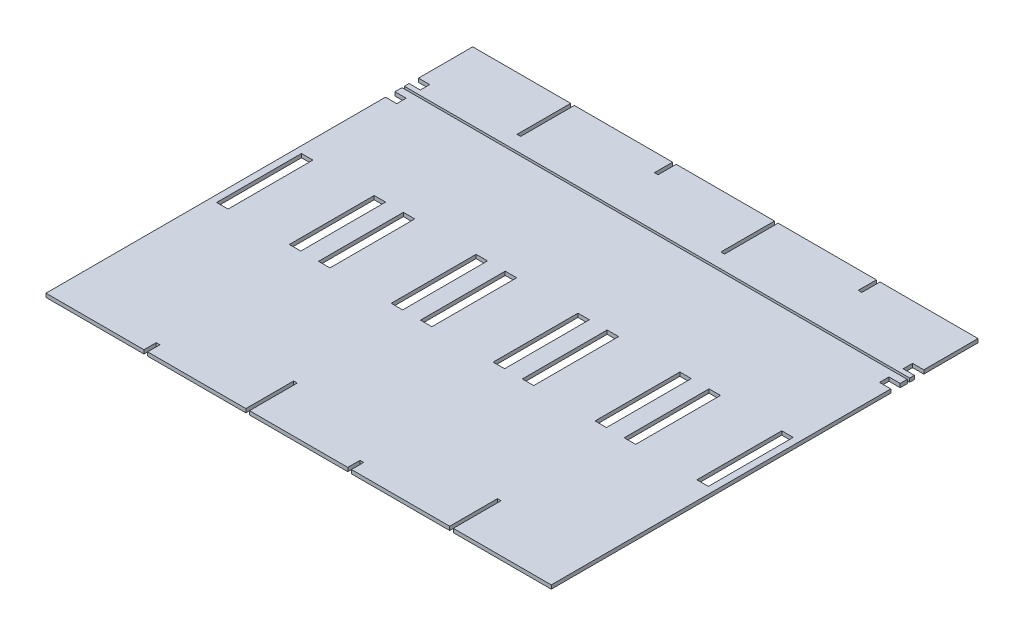
SolidWorks part; units mm, degrees
note: The reader was unsure of these and kept them because the rebuilt part matched: shared geometry of "Sketch1<4>".
ref_plane "Front Plane" through (0, 0, 0) normal (0, 0, 1) x (1, 0, 0)
ref_plane "Top Plane" through (0, 0, 0) normal (0, 1, 0) x (1, 0, 0)
ref_plane "Right Plane" through (0, 0, 0) normal (1, 0, 0) x (0, 0, -1)
sketch "Sketch1" plane through (0, 0, 0) normal (0, 1, 0) x (1, 0, 0)
  line L0 (-128.1196, -237.612) -> (-128.1196, 237.612)
  line L1 (214.312, 237.612) -> (-214.312, 237.612)
  line L2 (214.312, 237.612) -> (214.312, -237.612)
  line L3 (214.312, -237.612) -> (-214.312, -237.612)
  line L4 (-214.312, 237.612) -> (-214.312, -237.612)
  line L5 (214.312, 237.612) -> (-214.312, -237.612) construction
  line L6 (214.312, -237.612) -> (-214.312, 237.612) construction
  line L7 (131.2076, -237.612) -> (128.1196, -237.612)
  line L8 (131.2076, -237.612) -> (131.2076, 237.612)
  line L9 (131.2076, 237.612) -> (128.1196, 237.612)
  line L10 (128.1196, -237.612) -> (128.1196, 237.612)
  line L11 (-131.2076, -237.612) -> (-131.2076, 237.612)
  line L12 (44.7652, -237.612) -> (44.7652, 237.612)
  line L13 (41.6772, -237.612) -> (41.6772, 237.612)
  line L14 (-41.6772, -237.612) -> (-41.6772, 237.612)
  line L15 (-44.7652, -237.612) -> (-44.7652, 237.612)
  line L16 (-131.2076, -170.612) -> (-128.1196, -170.612)
  line L17 (-131.2076, 140.472) -> (-128.1196, 140.472)
  line L18 (-44.7652, 170.612) -> (-41.6772, 170.612)
  line L19 (41.6772, 140.472) -> (44.7652, 140.472)
  line L20 (128.1196, 170.612) -> (131.2076, 170.612)
  line L21 (-44.7652, -140.472) -> (-41.6772, -140.472)
  line L22 (41.6772, -170.612) -> (44.7652, -170.612)
  line L23 (128.1196, -140.472) -> (131.2076, -140.472)
  line L24 (214.312, 294.2232) -> (-214.312, 294.2232)
  line L25 (214.312, -181.0008) -> (-214.312, -181.0008)
  line L26 (214.312, 181.0008) -> (-214.312, 181.0008)
  line L27 (214.312, -294.2232) -> (-214.312, -294.2232)
  line L28 (-214.312, -53.1684) -> (-131.2076, -53.1684) construction
  line L29 (-128.1196, -100.5261) -> (-44.7652, -100.5261) construction
  line L30 (-41.6772, 121.0008) -> (41.6772, 121.0008) construction
  line L31 (44.7652, -53.1684) -> (128.1196, -53.1684) construction
  line L32 (131.2076, 25.4024) -> (214.312, 25.4024) construction
  line L33 (-214.312, 121.0008) -> (214.312, 121.0008)
  line L34 (-128.1196, 161.0008) -> (-44.7652, 161.0008) construction
  line L35 (44.7652, 161.0008) -> (128.1196, 161.0008)
  line L36 (-131.2076, 135.472) -> (-128.1196, 135.472)
  line L37 (-44.7652, 165.612) -> (-41.6772, 165.612)
  line L38 (41.6772, 135.472) -> (44.7652, 135.472)
  line L39 (128.1196, 165.612) -> (131.2076, 165.612)
  line L40 (0, 0) -> (0, 237.612) construction
  line L41 (214.312, 127.0008) -> (204.787, 127.0008)
  line L42 (214.312, 127.0008) -> (214.312, 135.0008)
  line L43 (214.312, 135.0008) -> (204.787, 135.0008)
  line L44 (204.787, 127.0008) -> (204.787, 135.0008)
  line L45 (204.787, 115.0008) -> (204.787, 107.0008)
  line L46 (214.312, 107.0008) -> (204.787, 107.0008)
  line L47 (214.312, 115.0008) -> (204.787, 115.0008)
  line L48 (-214.312, 107.0008) -> (-204.787, 107.0008)
  line L49 (-204.787, 115.0008) -> (-204.787, 107.0008)
  line L50 (-214.312, 115.0008) -> (-204.787, 115.0008)
  line L51 (-214.312, 127.0008) -> (-204.787, 127.0008)
  line L52 (-204.787, 127.0008) -> (-204.787, 135.0008)
  line L53 (-214.312, 135.0008) -> (-204.787, 135.0008)
  line L54 (-214.312, 123.0008) -> (214.312, 123.0008)
  line L55 (-198.8776, 29.96) -> (-146.8776, 29.96) construction
  line L56 (-208.5776, 29.96) -> (-198.8776, 29.96)
  line L57 (-208.5776, 29.96) -> (-208.5776, -42)
  line L58 (-208.5776, -42) -> (-198.8776, -42)
  line L59 (-198.8776, 29.96) -> (-198.8776, -42)
  line L60 (-146.8776, 29.96) -> (-137.1776, 29.96)
  line L61 (-146.8776, 29.96) -> (-146.8776, -42)
  line L62 (-146.8776, -42) -> (-137.1776, -42)
  line L63 (-137.1776, 29.96) -> (-137.1776, -42)
  line L64 (-198.8776, -42) -> (-146.8776, -42) construction
  line L65 (-214.312, 0) -> (-214.312, -42)
  line L66 (-214.312, -42) -> (-208.5776, -42) construction
  line L67 (-122.1376, 29.96) -> (-122.1376, -42)
  line L68 (-122.1376, 29.96) -> (-112.4376, 29.96)
  line L69 (-112.4376, 29.96) -> (-112.4376, -42)
  line L70 (-122.1376, -42) -> (-112.4376, -42)
  line L71 (-60.4376, 29.96) -> (-60.4376, -42)
  line L72 (-60.4376, 29.96) -> (-50.7376, 29.96)
  line L73 (-50.7376, 29.96) -> (-50.7376, -42)
  line L74 (-60.4376, -42) -> (-50.7376, -42)
  line L75 (-35.6976, 29.96) -> (-35.6976, -42)
  line L76 (-35.6976, 29.96) -> (-25.9976, 29.96)
  line L77 (-25.9976, 29.96) -> (-25.9976, -42)
  line L78 (-35.6976, -42) -> (-25.9976, -42)
  line L79 (26.0024, 29.96) -> (26.0024, -42)
  line L80 (26.0024, 29.96) -> (35.7024, 29.96)
  line L81 (35.7024, 29.96) -> (35.7024, -42)
  line L82 (26.0024, -42) -> (35.7024, -42)
  line L83 (50.7424, 29.96) -> (50.7424, -42)
  line L84 (50.7424, 29.96) -> (60.4424, 29.96)
  line L85 (60.4424, 29.96) -> (60.4424, -42)
  line L86 (50.7424, -42) -> (60.4424, -42)
  line L87 (112.4424, 29.96) -> (112.4424, -42)
  line L88 (112.4424, 29.96) -> (122.1424, 29.96)
  line L89 (122.1424, 29.96) -> (122.1424, -42)
  line L90 (112.4424, -42) -> (122.1424, -42)
  line L91 (137.1824, 29.96) -> (137.1824, -42)
  line L92 (137.1824, 29.96) -> (146.8824, 29.96)
  line L93 (146.8824, 29.96) -> (146.8824, -42)
  line L94 (137.1824, -42) -> (146.8824, -42)
  line L95 (198.8824, 29.96) -> (198.8824, -42)
  line L96 (198.8824, 29.96) -> (208.5824, 29.96)
  line L97 (208.5824, 29.96) -> (208.5824, -42)
  line L98 (198.8824, -42) -> (208.5824, -42)
  point P0 (0, 0)
  dimension "D9" = 5
  dimension "D21" = 9.525
  dimension "D1" = 475.224
  dimension "D2" = 428.624
  dimension "D3" = 3.088
  dimension "D4" = 60
  dimension "D5" = 3.088
  dimension "D6" = 3.088
  dimension "D7" = 3.088
  dimension "D8" = 40
  dimension "D10" = 40
  dimension "D11" = 67
  dimension "D12" = 67
  dimension "D13" = 67
  dimension "D14" = 67
  dimension "D15" = 97.14
  dimension "D16" = 97.14
  dimension "D17" = 97.14
  dimension "D18" = 97.14
  dimension "D22" = 83.3544
  dimension "D23" = 8
  dimension "D24" = 6
  dimension "D26" = 52
  dimension "D27" = 5.97
  dimension "D28" = 9.7
  dimension "D29" = 42
  dimension "D30" = 71.96
  dimension "D32" = 86.44
  dimension "D19" = 56.6112
  dimension "D20" = 56.6112
  dimension "D25" = 2
  dimension "D31" = 5
extrude "Boss-Extrude1" add sketch "Sketch1" along normal blind 3.175 contours L2 L26 L8 L25 | L10 L26 L12 L25 | L13 L26 L14 L25 | L15 L26 L0 L25 | L14 L26 L15 L21 | L25 L0 L17 L11 | L33 L4 L25 L11 | L33 L13 L25 L12 | L33 L10 L23 L8
extrude "Boss-Extrude2" add sketch "Sketch1<4>" along direction (0, 1, 0) on the side of the normal up to surface (3.175 mm away) separate body
sketch "Sketch1<4>" plane through (0, 0, 0) normal (0, 1, 0) x (1, 0, 0) same geometry as "Sketch1"
